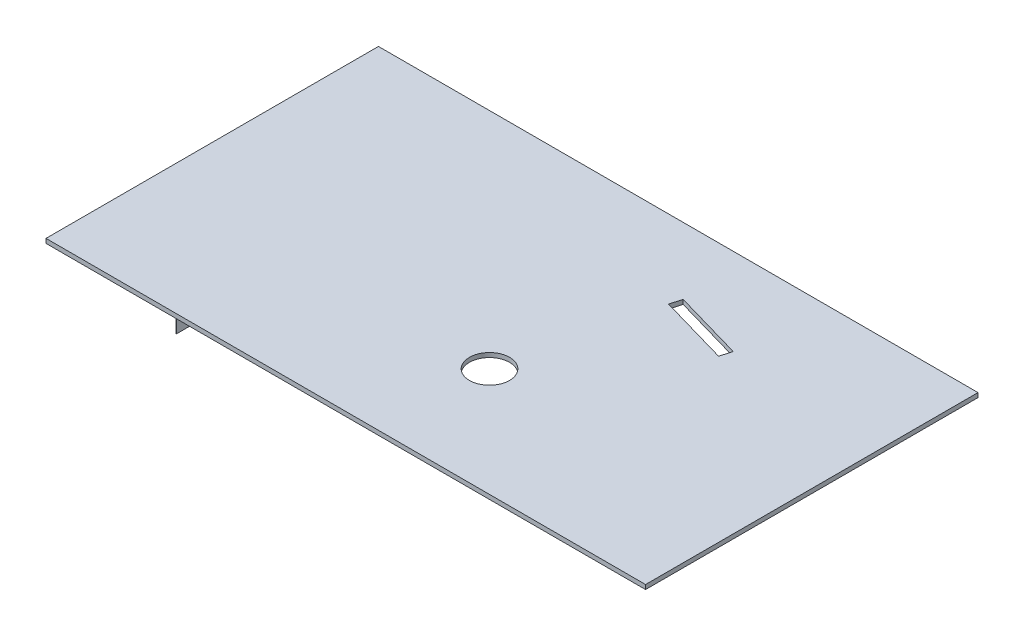
SolidWorks part; units mm, degrees
material "Particle Board"
ref_plane "Front Plane" through (0, 0, 0) normal (0, 0, 1) x (1, 0, 0)
ref_plane "Top Plane" through (0, 0, 0) normal (0, 1, 0) x (1, 0, 0)
ref_plane "Right Plane" through (0, 0, 0) normal (1, 0, 0) x (0, 0, -1)
sketch "Sketch3" plane through (0, 0, 0) normal (0, 1, 0) x (1, 0, 0)
  line L1 (0, 0) -> (-839.8654, 0) construction
  line L2 (0, 0) -> (-451.1992, 260.5) construction
  line L5 (-524, 0) -> (-525.5875, 0)
  line L6 (277.6777, 444.3772) -> (277.6777, 446.248)
  circle A0 centre (0, 0) radius 254 construction
  arc A3 (277.6777, 444.3772) -> (-524, 0) centre (0, 0) ccw
  arc A4 (277.6777, 446.248) -> (-525.5875, 0) centre (0, 0) ccw
  arc A5 (278.5189, 445.7235) -> (-525.5875, 0) centre (0, 0) ccw construction
  dimension "D1" = 524
  dimension "D2" = 1.5875
  dimension "D4" = 122
  dimension "D5" = 508
  dimension "D3" = 30
extrude "Boss-Extrude1" add sketch "Sketch3" along normal blind 50.8
sketch "Sketch4" plane through (0, 50.8, 0) normal (0, 1, 0) x (1, 0, 0)
  line L5 (-848, 566.7) -> (670.6777, 566.7)
  line L6 (-848, 566.7) -> (-848, -275.4)
  line L7 (-848, -275.4) -> (670.6777, -275.4)
  line L8 (670.6777, 566.7) -> (670.6777, -275.4)
  dimension "D1" = 275.4
  dimension "D2" = 848
  dimension "D3" = 566.7
  dimension "D4" = 393
extrude "Boss-Extrude2" add sketch "Sketch4" against normal blind 11.1125
hole_wizard "Ø20.0mm Dowel Hole1" positions "Sketch6" profile "Sketch7" hole size "Ø20.0" standard "ANSI Metric" end condition through all
sketch "Sketch6" plane through (0, 50.8, 0) normal (0, 1, 0) x (1, 0, 0)
  point P0 (0, 0)
sketch "Sketch7" plane through (0, 50.8, 0) normal (1, 0, 0) x (0, 0, 1)
  line L0 (0, 0) -> (0, 50.8)
  line L1 (0, 50.8) -> (50.8, 50.8)
  line L2 (50.8, 50.8) -> (50.8, 0)
  line L5 (50.8, 0) -> (0, 0)
  line L11 (0, -6.35) -> (0, 107.95) construction
  dimension "Thru Hole Dia." = 101.6
  dimension "Thru Hole Depth" = 50.8
ref_plane "Plane1" through (0, 0, 269.05) normal (0, 0, 1) x (1, 0, 0)
sketch "Sketch8" plane through (0, 0, 0) normal (0, 0, 1) x (1, 0, 0)
  line L0 (-524, 39.6875) -> (-524, 0) construction
  line L1 (-525.5875, 39.6875) -> (-524, 39.6875)
  line L2 (-525.5875, 39.6875) -> (-525.5875, 0)
  line L3 (-525.5875, 0) -> (-524, 0)
  line L4 (-524, 39.6875) -> (-524, 0)
  line L5 (-525.5875, 39.6875) -> (-525.5875, 0) construction
  line L6 (-525.5875, 0) -> (-524, 0) construction
extrude "Boss-Extrude3" add sketch "Sketch8" along normal up to surface (269.05 mm away) up to plane "Plane1"
sketch "Sketch9" plane through (0, 50.8, 0) normal (0, 1, 0) x (1, 0, 0)
  line L0 (270.6691, 346.7379) -> (92.8357, 397.7308)
  line L1 (92.8357, 397.7308) -> (84.5666, 368.8929)
  line L2 (84.5666, 368.8929) -> (262.4, 317.9)
  line L3 (262.4, 317.9) -> (270.6691, 346.7379)
  line L6 (0, 0) -> (670.6777, 0) construction
  line L7 (670.6777, -275.4) -> (670.6777, 566.7) construction
  dimension "D1" = 185
  dimension "D2" = 30
  dimension "D3" = 16
  dimension "D4" = 262.4
  dimension "D5" = 317.9
extrude "Cut-Extrude1" cut sketch "Sketch9" against normal through all
sketch "Sketch10" plane through (0, 39.6875, 0) normal (0, 1, 0) x (1, 0, 0)
  line L0 (0, 0) -> (-545.6, 0) construction
  line L1 (0, 0) -> (277.6777, 444.3772) construction
  line L2 (0, 0) -> (195.5256, 509.3615) construction
  line L3 (0, 0) -> (94.7424, 537.3111) construction
  circle A0 centre (0, 0) radius 545.6 construction
  dimension "D1" = 11
  dimension "D2" = 11
